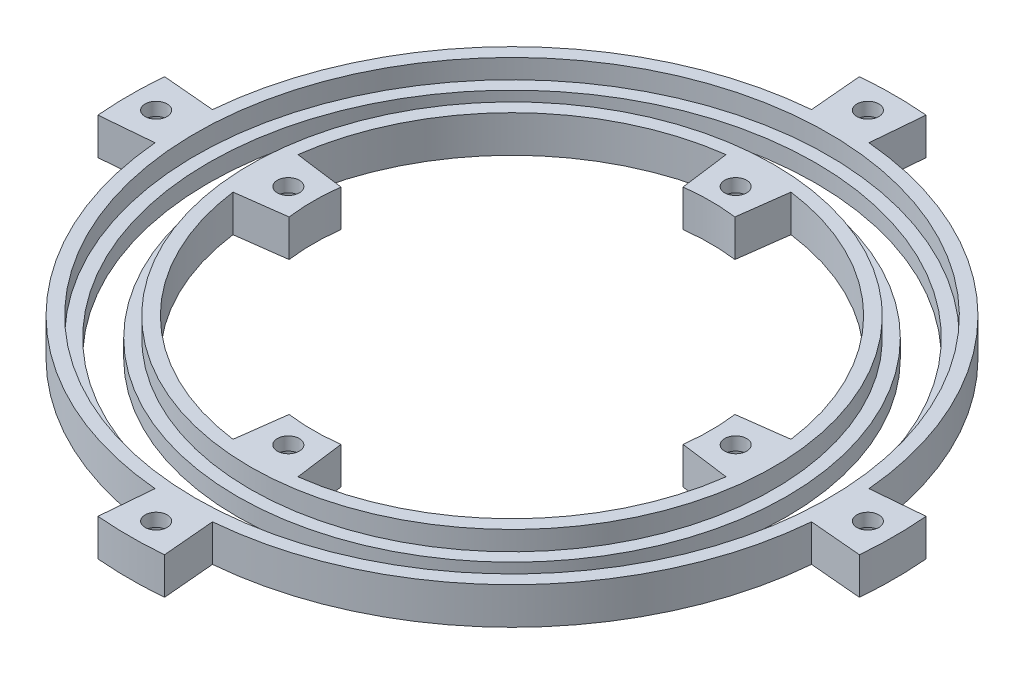
SolidWorks part; units mm, degrees
ref_plane "前视基准面" through (0, 0, 0) normal (0, 0, 1) x (1, 0, 0)
ref_plane "上视基准面" through (0, 0, 0) normal (0, 1, 0) x (1, 0, 0)
ref_plane "右视基准面" through (0, 0, 0) normal (1, 0, 0) x (0, 0, -1)
other "Configuration Table"
sketch "草图1" plane through (0, 0, 0) normal (0, 1, 0) x (1, 0, 0)
  line L0 (28.3, 0) -> (31.3, 0) construction
  line L2 (34.5, 0) -> (37.5, 0) construction
  circle A8 centre (0, 0) radius 37.5
  circle A9 centre (0, 0) radius 34.5
  circle A10 centre (0, 0) radius 31.3
  circle A11 centre (0, 0) radius 28.3
  dimension "D4" = 3.2
  dimension "D1" = 75
  dimension "D2" = 56.6
extrude "凸台-拉伸3" add sketch "草图1" along normal blind 4.2 contours A9 | A8 | A10 | A11
sketch "草图3" plane through (0, 4.2, 0) normal (0, 1, 0) x (1, 0, 0)
  circle A0 centre (0, 0) radius 36
  circle A4 centre (0, 0) radius 29.8
  circle A5 centre (0, 0) radius 34.5 construction
  circle A6 centre (0, 0) radius 31.3 construction
  dimension "D1" = 1.5
  dimension "D2" = 1.5
extrude "切除-拉伸1" cut sketch "草图3" against normal blind 2.2
sketch "草图4" plane through (0, 0, 0) normal (0, -1, 0) x (1, 0, 0)
  line L0 (0, 0) -> (-3.2683, 37.3573)
  line L1 (0, 37.5) -> (0, 43.5)
  line L2 (-3.2683, 37.3573) -> (-3.7913, 43.3345)
  line L3 (0, 0) -> (3.2683, 37.3573)
  line L4 (3.2683, 37.3573) -> (3.7913, 43.3345)
  line L5 (0, 37.5) -> (0, 0) construction
  line L7 (0, 0) -> (3.6939, 28.0579)
  circle A0 centre (0, 0) radius 43.5
  circle A1 centre (0, 0) radius 37.5 construction
  circle A2 centre (0, 40.5) radius 1.25
  circle A3 centre (0, 40.5) radius 2
  circle A4 centre (0, 0) radius 28.3 construction
  circle M8 centre (0, 0) radius 37.5
  dimension "D1" = 6
  dimension "D4" = 4
  dimension "D5" = 2.5
  dimension "D2" = 5
  dimension "D3" = 5
  dimension "D7" = 7.5
extrude "凸台-拉伸4" add sketch "草图4" against normal up to surface (4.2 mm away) contours A3 L1 A0 L2 M8 | A3 L1 L4 A0 M8 | L1 A3 A2 | L1 A3 A2 region at (-2.1568, 0, 40.5321) region at (2.1568, 0, 40.5321) region at (-1.9553, 0, 40.5) region at (0.0447, 0, 38.875) up to face at (0, 4.2, 36)
extrude "切除-拉伸2" cut sketch "草图4<3>" against normal offset from surface (2.7 mm away) 1.5 contours L1 A3 A2 | L1 A3 A2 region at (1.3826, 0, 41.8826) region at (-0.0447, 0, 42.125) up to face at (0, 4.2, 36)
sketch "草图4<3>" plane through (0, 0, 0) normal (0, -1, 0) x (1, 0, 0) same geometry as "草图4"
pattern_circular "阵列(圆周)2" count 4 over 360 about axis through (0, 4.2, 0) along (0, -1, 0) of "凸台-拉伸4", "切除-拉伸2" reverse direction yes
sketch "草图5" plane through (0, 0, 0) normal (0, -1, 0) x (1, 0, 0)
  line L0 (0, 28.3) -> (0, 22.611)
  line L1 (0, 22.611) -> (0, 0)
  line L2 (0, 0) -> (3.6939, 28.0579)
  line L3 (0, 0) -> (-3.6939, 28.0579)
  circle A0 centre (0, 0) radius 22.611
  circle A1 centre (0, 0) radius 28.3
  circle A2 centre (0, 0) radius 28.3 construction
  circle A3 centre (0, 25.4555) radius 1.25
  circle A4 centre (0, 25.4555) radius 2
  circle M12 centre (0, 0) radius 28.3
  dimension "D1" = 45.2219
  dimension "D4" = 4
  dimension "D5" = 2.5
  dimension "D2" = 7.5
  dimension "D3" = 7.5
extrude "凸台-拉伸5" add sketch "草图5" against normal up to surface (4.2 mm away) contours A4 L0 A0 L2 M12 | A4 L0 L3 A0 M12 | L0 A4 A3 | L0 A4 A3 region at (2.078, 0, 25.5049) region at (-2.078, 0, 25.5049) region at (1.3826, 0, 26.8381) region at (-0.0447, 0, 27.0805) up to face at (0, 4.2, 28.3)
extrude "切除-拉伸3" cut sketch "草图5<3>" against normal offset from surface (2.7 mm away) 1.5 contours A4 up to face at (0, 4.2, 11.1966)
sketch "草图5<3>" plane through (0, 0, 0) normal (0, -1, 0) x (1, 0, 0) same geometry as "草图5"
pattern_circular "阵列(圆周)3" count 4 over 360 about axis through (0, 4.2, 0) along (0, -1, 0) of "切除-拉伸3", "凸台-拉伸5" reverse direction yes
sketch "草图6" plane through (0, 0, 0) normal (0, -1, 0) x (1, 0, 0)
  circle A0 centre (0, 0) radius 34.55
  circle A1 centre (0, 0) radius 31.25
  circle A2 centre (0, 0) radius 31.3 construction
  circle A3 centre (0, 0) radius 34.5 construction
  point P3 (-2.2613, 1.8955)
  dimension "D1" = 0.05
  dimension "D2" = 0.05
extrude "切除-拉伸4" cut sketch "草图6" against normal through all
